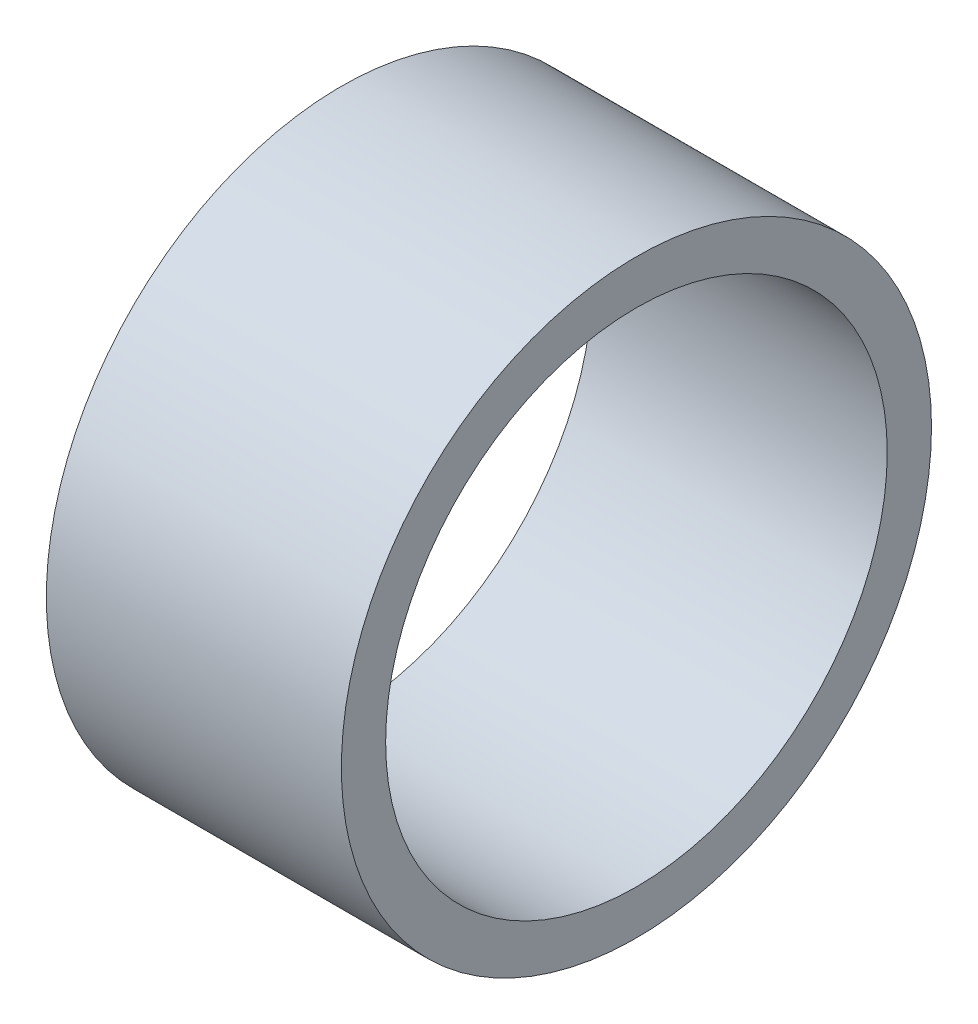
SolidWorks part; units mm, degrees
material "AISI 1020"
ref_plane "Front Plane" through (0, 0, 0) normal (0, 0, 1) x (1, 0, 0)
ref_plane "Top Plane" through (0, 0, 0) normal (0, 1, 0) x (1, 0, 0)
ref_plane "Right Plane" through (0, 0, 0) normal (1, 0, 0) x (0, 0, -1)
sketch "Sketch1" plane through (0, 0, 0) normal (1, 0, 0) x (0, 0, -1)
  circle A0 centre (0, 0) radius 25.4
  circle A1 centre (0, 0) radius 21.59
  dimension "D1" = 50.8
  dimension "D2" = 3.81
extrude "Boss-Extrude1" add sketch "Sketch1" along normal mid plane 25.4
